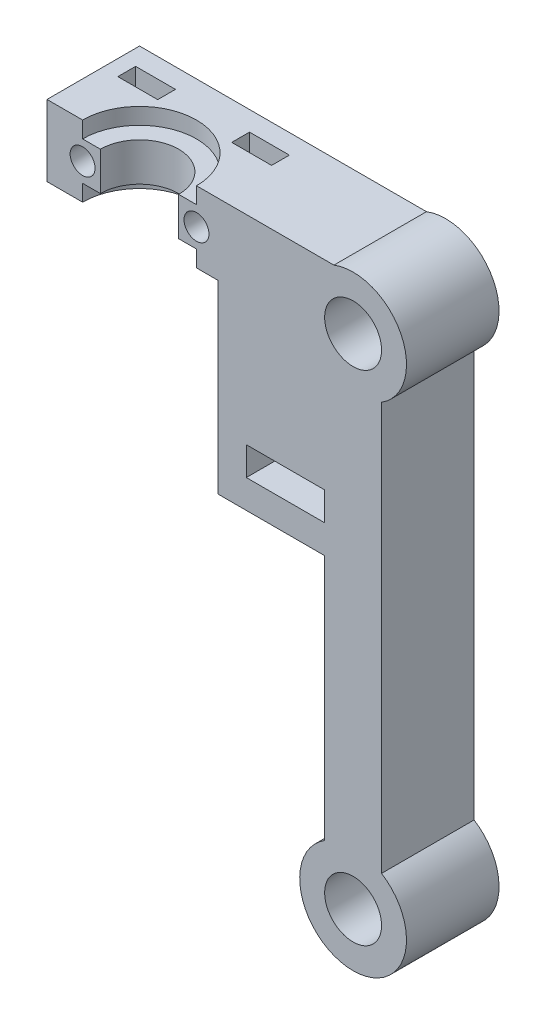
SolidWorks part; units mm, degrees
material "ABS"
ref_plane "Plano frontal" through (0, 0, 0) normal (0, 0, 1) x (1, 0, 0)
ref_plane "Plano superior" through (0, 0, 0) normal (0, 1, 0) x (1, 0, 0)
ref_plane "Plano direito" through (0, 0, 0) normal (1, 0, 0) x (0, 0, -1)
sketch "Esboço1" plane through (0, 0, 0) normal (0, 0, 1) x (1, 0, 0)
  line L0 (4, 63.6557) -> (4, 6.3443)
  line L1 (0, 70) -> (0, 0) construction
  line L2 (-2.6926, 77) -> (-19, 77)
  line L3 (-4, 41) -> (-19, 41)
  line L4 (-19, 41) -> (-19, 53)
  line L6 (-19, 77) -> (-19, 53)
  line L7 (-4, 41) -> (-4, 6.3443)
  line L8 (-15, 49) -> (-4, 49)
  line L9 (-15, 49) -> (-15, 45)
  line L10 (-15, 45) -> (-4, 45)
  line L11 (-4, 49) -> (-4, 45)
  line L12 (-15, 49) -> (-4, 45) construction
  line L13 (-15, 45) -> (-4, 49) construction
  circle A0 centre (0, 70) radius 4
  circle A1 centre (0, 0) radius 4
  arc A2 (4, 63.6557) -> (-2.6926, 77) centre (0, 70) ccw
  arc A3 (-4, 6.3443) -> (4, 6.3443) centre (0, 0) ccw
  point P4 (-4, 63.6557)
  point P6 (0, 0)
  point P14 (-9.5, 47)
  point P21 (-19, 47)
  dimension "D1" = 8
  dimension "D2" = 15
  dimension "D3" = 70
  dimension "D4" = 8
  dimension "D5" = 21
  dimension "D6" = 12
  dimension "D7" = 15
  dimension "D8" = 4
  dimension "D9" = 4
  dimension "D10" = 24
extrude "Ressalto-extrusão1" add sketch "Esboço1" along normal blind 13
sketch "Esboço5" plane through (0, 41, 0) normal (0, -1, 0) x (1, 0, 0)
  line L1 (-21, 13) -> (-19, 13)
  line L2 (-24.5, 13) -> (-21, 13)
  line L6 (-19, 13) -> (-19, 0)
  line L10 (-19, 0) -> (-43, 0)
  line L27 (-43, 0) -> (-43, 13)
  line L28 (-43, 13) -> (-35.5, 13)
  line L29 (-35.5, 13) -> (-24.5, 13) construction
  circle A0 centre (-30, 13) radius 9 construction
  arc A1 (-35.5, 13) -> (-24.5, 13) centre (-30, 13) ccw
  point P1 (-19, 13)
  dimension "D11" = 5.5
  dimension "D2" = 18
  dimension "D3" = 7.5
  dimension "D4" = 24
extrude "Ressalto-extrusão3" add sketch "Esboço5" along normal blind 10 from offset 36 offset against normal yes
sketch "Esboço7" plane through (0, 77, 0) normal (0, 1, 0) x (1, 0, 0)
  circle A0 centre (-30, -13) radius 8
  point P3 (0, 0)
  point P4 (-24.5, -15)
  dimension "D1" = 16
extrude "Corte-extrusão2" cut sketch "Esboço7" along normal blind 2.3 from offset 10 offset against normal yes
extrude "Corte-extrusão3" cut sketch "Esboço7<2>" against normal blind 2.3
sketch "Esboço7<2>" plane through (0, 77, 0) normal (0, 1, 0) x (1, 0, 0) same geometry as "Esboço7"
sketch "Esboço8" plane through (0, 77, 0) normal (0, 1, 0) x (1, 0, 0)
  line L0 (-38, -4) -> (-22, -4) construction
  line L1 (-40.8, -2.75) -> (-35.2, -2.75)
  line L2 (-40.8, -2.75) -> (-40.8, -5.25)
  line L3 (-40.8, -5.25) -> (-35.2, -5.25)
  line L4 (-35.2, -2.75) -> (-35.2, -5.25)
  line L5 (-40.8, -2.75) -> (-35.2, -5.25) construction
  line L6 (-40.8, -5.25) -> (-35.2, -2.75) construction
  line L7 (-24.8, -2.75) -> (-19.2, -2.75)
  line L8 (-24.8, -2.75) -> (-24.8, -5.25)
  line L9 (-24.8, -5.25) -> (-19.2, -5.25)
  line L10 (-19.2, -2.75) -> (-19.2, -5.25)
  line L11 (-24.8, -2.75) -> (-19.2, -5.25) construction
  line L12 (-24.8, -5.25) -> (-19.2, -2.75) construction
  line L13 (-36.5, -4) -> (-36.5, -14.5536) construction
  line L14 (-38, -13) -> (-43, -13) construction
  arc A0 (-22, -13) -> (-38, -13) centre (-30, -13) ccw construction
  point P0 (-38, -4)
  point P5 (-22, -4)
  point P12 (-30, -4)
  point P16 (-30, -5)
  dimension "D1" = 5.6
  dimension "D2" = 2.5
  dimension "D3" = 1.5
  dimension "D4" = 16
  dimension "D5" = 9
extrude "Corte-extrusão4" cut sketch "Esboço8" against normal blind 10
sketch "Esboço9" plane through (0, 0, 13) normal (0, 0, 1) x (1, 0, 0)
  line L0 (-22, 72) -> (-38, 72) construction
  line L1 (-22, 74.7) -> (-38, 74.7) construction
  line L2 (-35.5, 69.3) -> (-35.5, 74.7) construction
  circle A0 centre (-38, 72) radius 1.75
  circle A1 centre (-22, 72) radius 1.75
  point P4 (-30, 74.7)
  point P5 (-30, 72)
  point P10 (-35.5, 72)
  dimension "D1" = 3.5
  dimension "D2" = 16
extrude "Corte-extrusão5" cut sketch "Esboço9" against normal through all
